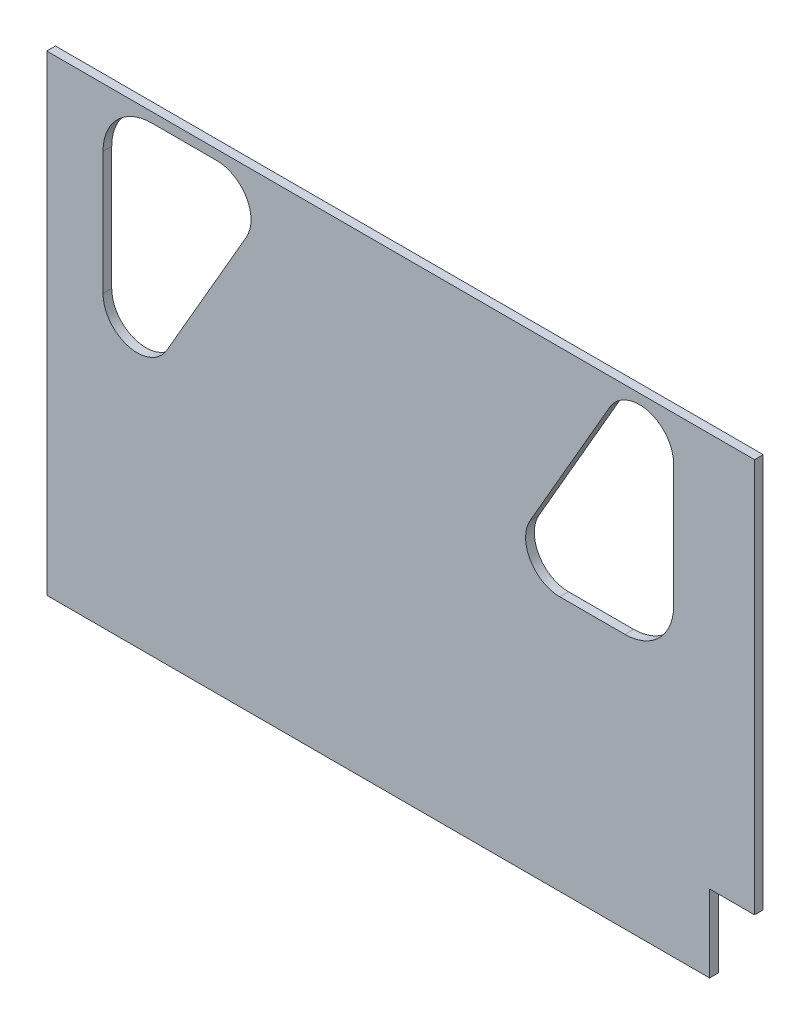
SolidWorks part; units mm, degrees
ref_plane "Front Plane" through (0, 0, 0) normal (0, 0, 1) x (1, 0, 0)
ref_plane "Top Plane" through (0, 0, 0) normal (0, 1, 0) x (1, 0, 0)
ref_plane "Right Plane" through (0, 0, 0) normal (1, 0, 0) x (0, 0, -1)
sketch "Sketch1" plane through (0, 0, 0) normal (0, 0, 1) x (1, 0, 0)
  line L1 (0, 0) -> (2285, 0)
  line L2 (0, 0) -> (0, 1625)
  line L3 (0, 1625) -> (2440, 1625)
  line L4 (2440, 266) -> (2440, 1625)
  line L7 (2440, 266) -> (2285, 266)
  line L8 (2285, 0) -> (2285, 266)
  dimension "D1" = 2440
  dimension "D2" = 1625
  dimension "D3" = 155
  dimension "D4" = 266
extrude "Boss-Extrude1" add sketch "Sketch1" along normal blind 30
extrude "Cut-Extrude1" cut sketch "Sketch2" against normal through all
sketch "Sketch2" plane through (441.9635, -561.6168, 31) normal (0, 0, 1) x (1, 0, 0)
  line L0 (1498.8454, 2093.6165) -> (1224.6054, 1618.6165)
  line L1 (1326.7965, 1441.6168) -> (1551.0365, 1441.6168)
  line L2 (1719.0365, 1609.6168) -> (1719.0365, 2034.6168)
  line L5 (-247.9635, 1984.6168) -> (-247.9635, 1559.6168)
  line L6 (-27.7724, 1500.617) -> (246.4676, 1975.617)
  line L7 (144.2765, 2152.6168) -> (-79.9635, 2152.6168)
  arc A0 (1551.0365, 1441.6168) -> (1719.0365, 1609.6168) centre (1551.0365, 1609.6168) ccw
  arc A1 (1498.8454, 2093.6165) -> (1719.0365, 2034.6168) centre (1601.0365, 2034.6168) cw
  arc A2 (1224.6054, 1618.6165) -> (1326.7965, 1441.6168) centre (1326.7965, 1559.6168) ccw
  arc A3 (-247.9635, 1559.6168) -> (-27.7724, 1500.617) centre (-129.9635, 1559.6168) ccw
  arc A4 (246.4676, 1975.617) -> (144.2765, 2152.6168) centre (144.2765, 2034.6168) ccw
  arc A5 (-247.9635, 1984.6168) -> (-79.9635, 2152.6168) centre (-79.9635, 1984.6168) cw
  point P22 (54.1362, 1500.617)
